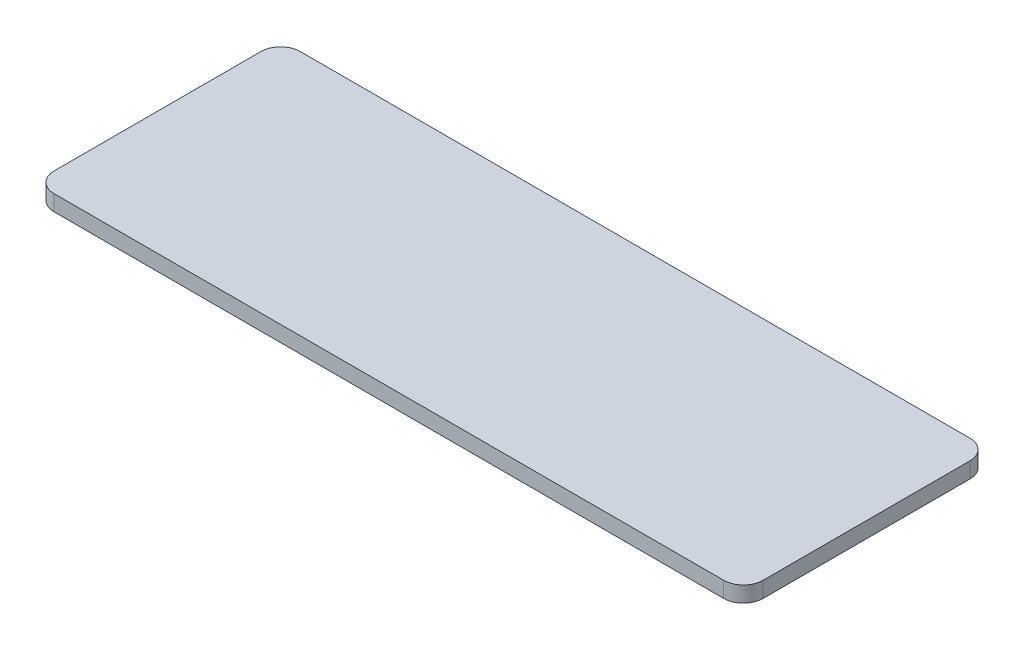
SolidWorks part; units mm, degrees
ref_plane "Front Plane" through (0, 0, 0) normal (0, 0, 1) x (1, 0, 0)
ref_plane "Top Plane" through (0, 0, 0) normal (0, 1, 0) x (1, 0, 0)
ref_plane "Right Plane" through (0, 0, 0) normal (1, 0, 0) x (0, 0, -1)
sketch "Sketch1" plane through (0, 0, 0) normal (0, 1, 0) x (1, 0, 0)
  line L1 (0, 0) -> (72, 0)
  line L2 (0, 0) -> (0, 25)
  line L3 (0, 25) -> (72, 25)
  line L4 (72, 0) -> (72, 25)
  dimension "D1" = 72
  dimension "D2" = 25
extrude "Boss-Extrude1" add sketch "Sketch1" along normal blind 1.6
fillet "Fillet1" radius 2 4 edges at (0, 0.8, 0) (0, 0.8, -25) (72, 0.8, -25) (72, 0.8, 0)
